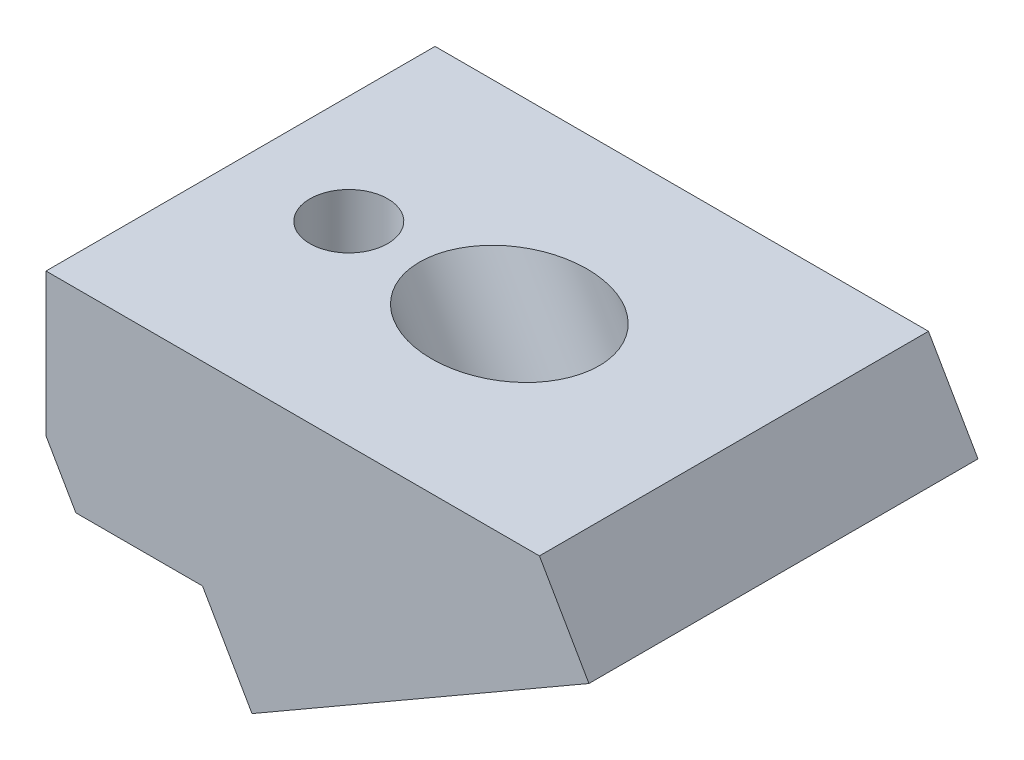
SolidWorks part; units mm, degrees
ref_plane "Plano frontal" through (0, 0, 0) normal (0, 0, 1) x (1, 0, 0)
ref_plane "Plano superior" through (0, 0, 0) normal (0, 1, 0) x (1, 0, 0)
ref_plane "Plano direito" through (0, 0, 0) normal (1, 0, 0) x (0, 0, -1)
sketch "Esboço1" plane through (0, 0, 0) normal (0, 1, 0) x (1, 0, 0)
  line L5 (-15, -15) -> (15, -15)
  line L6 (-15, -15) -> (-15, 15)
  line L7 (-15, 15) -> (15, 15)
  line L8 (15, -15) -> (15, 15)
  line L9 (-15, -15) -> (15, 15) construction
  line L10 (-15, 15) -> (15, -15) construction
  point P0 (0, 0)
  dimension "D1" = 30
  dimension "D2" = 30
extrude "Ressalto-extrusão1" add sketch "Esboço1" along normal blind 22.775
sketch "Esboço2" plane through (0, 0, 15) normal (0, 0, 1) x (1, 0, 0)
  line L7 (-15, 0) -> (15, 17.3205)
  line L8 (15, 22.775) -> (15, 0) construction
  line L9 (15, 17.3205) -> (15, 0)
  line L10 (15, 0) -> (-15, 0)
  line L11 (-15, 22.775) -> (15, 22.775) construction
  dimension "D1" = 30
extrude "Corte-extrusão1" cut sketch "Esboço2" against normal through all
sketch "Esboço3" plane through (-3.75, 6.4952, 0) normal (0.5, -0.866, 0) x (0.866, 0.5, 0)
  line L5 (21.6506, 15) -> (-12.9904, 15) construction
  line L7 (-10.6699, 15) -> (19.3301, 15)
  line L8 (-10.6699, 15) -> (-10.6699, -15)
  line L9 (-10.6699, -15) -> (19.3301, -15)
  line L10 (19.3301, 15) -> (19.3301, -15)
  line L11 (-10.6699, 15) -> (19.3301, -15) construction
  line L12 (-10.6699, -15) -> (19.3301, 15) construction
  line L13 (21.6506, -15) -> (21.6506, 15) construction
  point P0 (4.3301, 0)
  point P7 (21.6506, 0)
  point P12 (4.3301, 15)
  point P15 (19.3301, 0)
  dimension "D1" = 30
  dimension "D2" = 30
extrude "Corte-extrusão2" cut sketch "Esboço3" against normal through all flip side to cut
sketch "Esboço4" plane through (0, 0, 15) normal (0, 0, 1) x (1, 0, 0)
  line L0 (-25.4697, 22.775) -> (-15, 4.641)
  line L1 (-25.4697, 22.775) -> (-15, 22.775)
  line L2 (-15, 22.775) -> (9.1714, 22.775) construction
  line L3 (-15, 4.641) -> (-12.9904, 1.1603) construction
  line L4 (-15, 22.775) -> (-15, 4.641) construction
  line L5 (-15, 22.775) -> (-15, 4.641)
extrude "Ressalto-extrusão2" add sketch "Esboço4" against normal blind 30
sketch "Esboço5" plane through (-3.75, 6.4952, 0) normal (0.5, -0.866, 0) x (-0.866, -0.5, 0)
  circle A0 centre (-4.3301, 0) radius 3.95
  dimension "D1" = 7.9
extrude "Corte-extrusão3" cut sketch "Esboço5" against normal through all
sketch "Esboço6" plane through (0, 0, 15) normal (0, 0, 1) x (1, 0, 0)
  line L0 (12.9904, 16.1603) -> (-21.6506, 16.1603) construction
  line L2 (-25.4697, 22.775) -> (-12.9904, 1.1603) construction
  line L3 (-2.0096, 16.1603) -> (-2.0096, 22.775) construction
  line L5 (-25.4697, 22.775) -> (9.1714, 22.775) construction
  dimension "D1" = 15
sketch "Esboço8" plane through (-3.75, 6.4952, 0) normal (0.5, -0.866, 0) x (0.866, 0.5, 0)
  circle A0 centre (4.3301, 0) radius 6
  dimension "D1" = 12
extrude "Corte-extrusão5" cut sketch "Esboço8" against normal blind 25 from offset 8 offset against normal yes
sketch "Esboço9" plane through (0, 22.775, 0) normal (0, 1, 0) x (1, 0, 0)
  line L0 (-15.0774, 0) -> (-16.5774, 0) construction
  circle A0 centre (-20.5274, 0) radius 3.95 construction
  circle A1 centre (-20.5274, 0) radius 3.95 construction
  circle A2 centre (-20.5274, 0) radius 3.95
  ellipse E0 centre (-8.1491, 0) end of major axis (-15.0774, 0) minor radius 6 construction
  point P3 (-16.5774, 0)
  point P8 (-15.0774, 0)
  dimension "D1" = 7.9
  dimension "D2" = 0
  dimension "D3" = 1.5
extrude "Corte-extrusão6" cut sketch "Esboço9" against normal blind 10
sketch "Esboço10" plane through (0, 22.775, 0) normal (0, 1, 0) x (1, 0, 0)
  line L0 (-25.4697, 15) -> (-40.7856, 15)
  line L1 (-40.7856, 15) -> (-40.7856, -15)
  line L2 (-40.7856, -15) -> (-25.4697, -15)
  line L3 (-25.4697, 3.9373) -> (-25.4697, -3.9373)
  line L4 (-25.4697, 15) -> (-25.4697, 3.9373)
  line L5 (-25.4697, -15) -> (-25.4697, -3.9373)
  point P0 (0, 0)
  point P6 (-25.7856, -3.95)
extrude "Ressalto-extrusão3" add sketch "Esboço10" against normal blind 15 separate body
sketch "Esboço11" plane through (-25.4697, 0, 0) normal (1, 0, 0) x (0, 0, -1)
  line L1 (-15, 22.775) -> (15, 22.775)
  line L2 (-15, 22.775) -> (-15, 7.775)
  line L3 (-15, 7.775) -> (15, 7.775)
  line L4 (15, 22.775) -> (15, 7.775)
extrude "Ressalto-extrusão4" add sketch "Esboço11" along normal blind 10
extrude "Corte-extrusão7" cut sketch "Esboço9<2>" against normal blind 30
sketch "Esboço9<2>" plane through (0, 22.775, 0) normal (0, 1, 0) x (1, 0, 0) same geometry as "Esboço9"
sketch "Esboço7" plane through (0, 22.775, 0) normal (0, 1, 0) x (1, 0, 0)
  line L0 (-12.9904, 0) -> (-12.9904, -15) construction
  line L1 (-25.4697, 15) -> (-25.4697, -15) construction
  circle A0 centre (-12.9904, 0) radius 3.95
  point P6 (-25.4697, 0)
  dimension "D1" = 7.9
extrude "Corte-extrusão4" [suppressed] cut sketch "Esboço7" against normal through all
sketch "Esboço12" plane through (0, 7.775, 0) normal (0, -1, 0) x (1, 0, 0)
  circle A0 centre (-20.5274, 0) radius 5.35
  circle A1 centre (-20.5274, 0) radius 3.95 construction
  point P3 (0, 0)
  dimension "D1" = 10.7
extrude "Corte-extrusão8" cut sketch "Esboço12" against normal blind 3.5 and the other way blind 10
sketch "Esboço13" plane through (0, 7.775, 0) normal (0, -1, 0) x (1, 0, 0)
  line L0 (-16.8094, -15) -> (-40.7856, -15) construction
  line L1 (-40.7856, 15) -> (-28.8774, 15)
  line L2 (-40.7856, 15) -> (-40.7856, -15)
  line L3 (-40.7856, -15) -> (-28.8774, -15)
  line L4 (-28.8774, 15) -> (-28.8774, -15)
  circle A0 centre (-20.5274, 0) radius 5.35 construction
  point P0 (-25.8774, 0)
  dimension "D1" = 3
extrude "Corte-extrusão9" cut sketch "Esboço13" against normal blind 23.5
sketch "Esboço14" plane through (0, 11.275, 0) normal (0, -1, 0) x (1, 0, 0)
  circle A0 centre (-20.5274, 0) radius 3
  circle A1 centre (-20.5274, 0) radius 3.95
  circle A2 centre (-20.5274, 0) radius 3.95 construction
  dimension "D1" = 6
  dimension "D2" = 0
extrude "Ressalto-extrusão5" add sketch "Esboço14" against normal up to surface (11.5 mm away) up to face at (-20.5274, 22.775, 3.95)
sketch "Esboço15" plane through (0, 0, 15) normal (0, 0, 1) x (1, 0, 0)
  line L0 (-12.9904, 1.1603) -> (-27.369, 26.0647) construction
  line L1 (-38.6555, 28.6981) -> (-22.9224, 1.4476)
  line L2 (-16.8094, 7.775) -> (-12.9904, 1.1603) construction
  line L3 (-38.6555, 28.6981) -> (-38.6555, 1.4476)
  line L4 (-38.6555, 1.4476) -> (-22.9224, 1.4476)
extrude "Corte-extrusão10" cut sketch "Esboço15" against normal up to surface (30 mm away) up to face at (-10.8988, 13.0701, -15)
